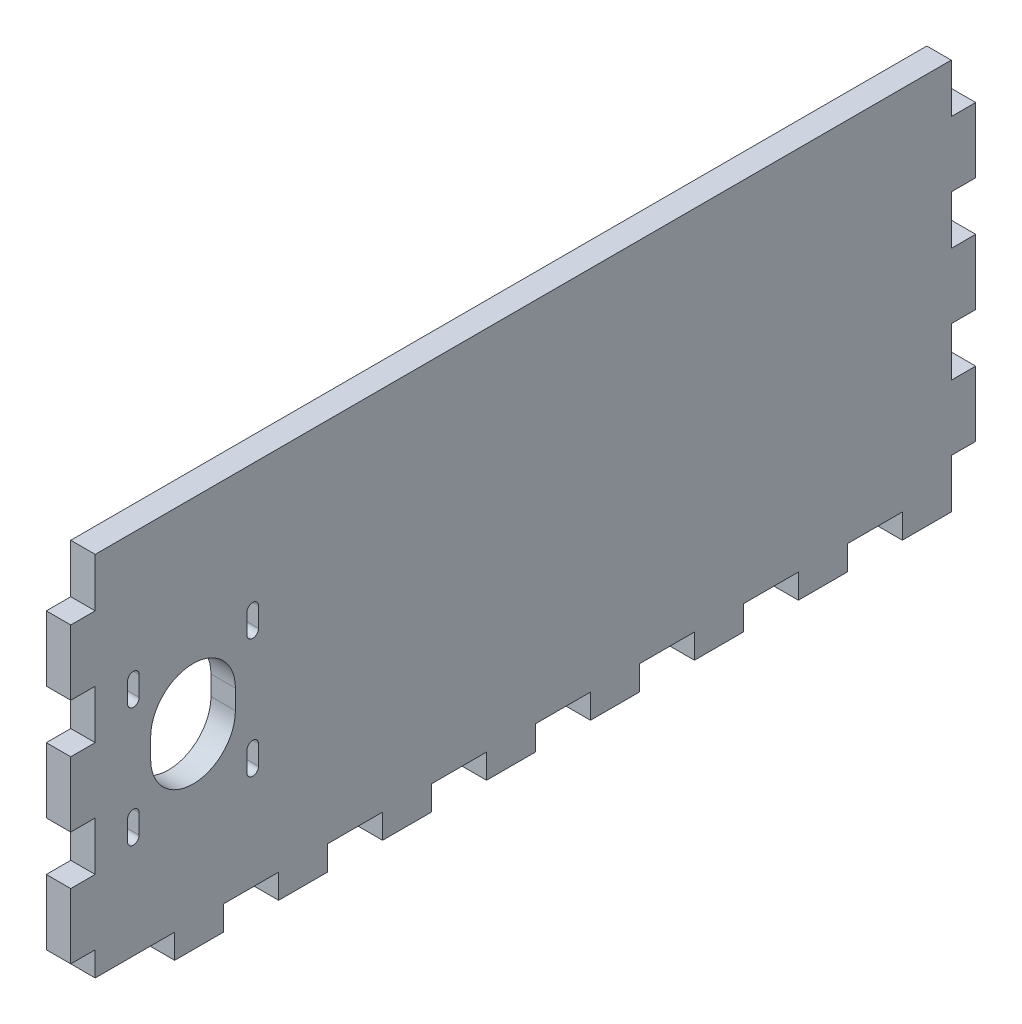
SolidWorks part; units mm, degrees
material "Acrylic (Medium-high impact)"
ref_plane "Front" through (0, 0, 0) normal (0, 0, 1) x (1, 0, 0)
ref_plane "Top" through (0, 0, 0) normal (0, 1, 0) x (1, 0, 0)
ref_plane "Right" through (0, 0, 0) normal (1, 0, 0) x (0, 0, -1)
sketch "Sketch1" plane through (0, 0, 0) normal (0, 0, 1) x (1, 0, 0)
  line L0 (0, 143.002) -> (0, -143.002) construction
  line L1 (-3.302, 133.858) -> (-3.302, -143.002)
  line L2 (-3.302, -143.002) -> (3.302, -143.002)
  line L3 (3.302, 143.002) -> (3.302, -143.002)
  line L4 (3.302, 143.002) -> (-16.256, 143.002)
  line L5 (-5.842, 136.398) -> (-16.256, 136.398)
  line L6 (-16.256, 143.002) -> (-16.256, 136.398)
  line L8 (-28.956, 155.448) -> (16.002, 155.448)
  line L9 (-28.956, 155.448) -> (-28.956, -149.352)
  line L10 (-28.956, -149.352) -> (16.002, -149.352)
  line L11 (16.002, 155.448) -> (16.002, -149.352)
  arc A0 (-3.302, 133.858) -> (-5.842, 136.398) centre (-5.842, 133.858) ccw
  point P2 (0, -143.002)
  point P11 (0, 0)
  dimension "D5" = 2.54
  dimension "D1" = 6.604
  dimension "D2" = 12.954
  dimension "D3" = 6.604
  dimension "D4" = 286.004
  dimension "D6" = 304.8
  dimension "D7" = 6.35
  dimension "D8" = 12.7
  dimension "D9" = 12.7
extrude "Boss-Extrude1" add sketch "Sketch1" along normal blind 6.35
sketch "Sketch2" plane through (16.002, 0, 0) normal (1, 0, 0) x (0, 0, -1)
  line L0 (-6.35, -149.352) -> (-6.35, 155.448) construction
  line L1 (-6.35, -47.752) -> (228.6, -47.752)
  line L2 (-6.35, -47.752) -> (-6.35, -149.352)
  line L3 (-6.35, -149.352) -> (228.6, -149.352)
  line L4 (228.6, -47.752) -> (228.6, -149.352)
  line L5 (14.4, -101.092) -> (14.4, -96.012)
  line L6 (36.4, -96.012) -> (36.4, -101.092)
  line L7 (8.4, -116.592) -> (8.4, -111.512)
  line L8 (11.4, -116.592) -> (11.4, -111.512)
  line L9 (8.4, -85.592) -> (8.4, -80.512)
  line L10 (11.4, -85.592) -> (11.4, -80.512)
  line L11 (25.4, -96.012) -> (25.4, -101.092) construction
  line L12 (42.4, -116.592) -> (42.4, -111.512)
  line L13 (39.4, -116.592) -> (39.4, -111.512)
  line L14 (39.4, -85.592) -> (39.4, -80.512)
  line L15 (42.4, -85.592) -> (42.4, -80.512)
  line L16 (0, -149.352) -> (0, 155.448) construction
  line L17 (225.425, -60.452) -> (225.425, -77.3853) construction
  line L18 (228.6, -47.752) -> (222.25, -47.752)
  line L19 (228.6, -47.752) -> (228.6, -60.452)
  line L20 (228.6, -60.452) -> (222.25, -60.452)
  line L21 (222.25, -47.752) -> (222.25, -60.452)
  line L22 (228.6, -107.0187) -> (222.25, -107.0187)
  line L23 (228.6, -107.0187) -> (228.6, -119.7187)
  line L24 (228.6, -119.7187) -> (222.25, -119.7187)
  line L25 (222.25, -107.0187) -> (222.25, -119.7187)
  line L26 (228.6, -136.652) -> (222.25, -136.652)
  line L27 (228.6, -136.652) -> (228.6, -149.352)
  line L28 (228.6, -149.352) -> (222.25, -149.352)
  line L29 (222.25, -136.652) -> (222.25, -149.352)
  line L30 (228.6, -77.3853) -> (222.25, -77.3853)
  line L31 (228.6, -77.3853) -> (228.6, -90.0853)
  line L32 (228.6, -90.0853) -> (222.25, -90.0853)
  line L33 (222.25, -77.3853) -> (222.25, -90.0853)
  line L34 (225.425, -90.0853) -> (225.425, -107.0187) construction
  line L35 (225.425, -119.7187) -> (225.425, -136.652) construction
  arc A0 (14.4, -101.092) -> (36.4, -101.092) centre (25.4, -101.092) ccw
  arc A1 (36.4, -96.012) -> (14.4, -96.012) centre (25.4, -96.012) ccw
  arc A2 (8.4, -116.592) -> (11.4, -116.592) centre (9.9, -116.592) ccw
  arc A3 (11.4, -111.512) -> (8.4, -111.512) centre (9.9, -111.512) ccw
  arc A4 (8.4, -85.592) -> (11.4, -85.592) centre (9.9, -85.592) ccw
  arc A5 (11.4, -80.512) -> (8.4, -80.512) centre (9.9, -80.512) ccw
  arc A6 (42.4, -116.592) -> (39.4, -116.592) centre (40.9, -116.592) cw
  arc A7 (39.4, -111.512) -> (42.4, -111.512) centre (40.9, -111.512) cw
  arc A8 (42.4, -85.592) -> (39.4, -85.592) centre (40.9, -85.592) cw
  arc A9 (39.4, -80.512) -> (42.4, -80.512) centre (40.9, -80.512) cw
  point P44 (25.4, -98.552)
  point P47 (-6.35, -98.552)
  line M17 (0, -149.352) -> (0, 155.448)
  line M19 (-6.35, 155.448) -> (-6.35, -149.352)
  line M20 (-6.35, -149.352) -> (0, -149.352)
  dimension "D1" = 22
  dimension "D6" = 1.5
  dimension "D10" = 1.5
  dimension "D2" = 5.08
  dimension "D3" = 5.08
  dimension "D4" = 15.5
  dimension "D5" = 15.5
  dimension "D7" = 15.5
  dimension "D8" = 15.5
  dimension "D9" = 5.08
  dimension "D11" = 25.4
  dimension "D12" = 50.8
  dimension "D13" = 203.2
  dimension "D14" = 12.7
  dimension "D15" = 6.35
extrude "Boss-Extrude2" add sketch "Sketch2" against normal blind 6.35 contours L33 L30 L4 L20 L21 L1 L3 L29 L26 L24 L25 L22 L32 A5 L10 A4 L9 A3 L8 A2 L7 A1 L6 A0 L5 L13 A7 L12 A6 L14 A9 L15 A8 M17 | L1 M19 M20 M17 region at (16.002, -98.552, -115.0085) region at (16.002, -98.552, 3.175)
sketch "Sketch3" plane through (9.652, 0, 0) normal (-1, 0, 0) x (0, 0, 1)
  line L0 (-222.25, -136.652) -> (-222.25, -149.352) construction
  line L1 (-222.25, -143.002) -> (0, -143.002)
  line L2 (-222.25, -143.002) -> (-222.25, -149.352)
  line L3 (-222.25, -149.352) -> (0, -149.352)
  line L4 (0, -143.002) -> (0, -149.352)
  dimension "D1" = 6.35
extrude "Boss-Extrude3" add sketch "Sketch3" along normal up to surface (38.608 mm away) up to face at (-28.956, 3.048, 3.175)
sketch "Sketch4" plane through (0, -149.352, 0) normal (0, -1, 0) x (1, 0, 0)
  line L0 (9.652, -20.6375) -> (9.652, -33.3375)
  line L1 (16.002, 6.35) -> (9.652, 6.35)
  line L2 (16.002, 6.35) -> (16.002, -6.35)
  line L3 (16.002, -6.35) -> (9.652, -6.35)
  line L4 (9.652, 6.35) -> (9.652, -6.35)
  line L5 (16.002, -20.6375) -> (9.652, -20.6375)
  line L6 (16.002, -20.6375) -> (16.002, -33.3375)
  line L7 (16.002, -33.3375) -> (9.652, -33.3375)
  line L8 (9.652, -47.625) -> (9.652, -60.325)
  line L9 (16.002, -47.625) -> (9.652, -47.625)
  line L10 (16.002, -47.625) -> (16.002, -60.325)
  line L11 (16.002, -60.325) -> (9.652, -60.325)
  line L12 (9.652, -74.6125) -> (9.652, -87.3125)
  line L13 (16.002, -74.6125) -> (9.652, -74.6125)
  line L14 (16.002, -74.6125) -> (16.002, -87.3125)
  line L15 (16.002, -87.3125) -> (9.652, -87.3125)
  line L16 (9.652, -101.6) -> (9.652, -114.3)
  line L17 (16.002, -101.6) -> (9.652, -101.6)
  line L18 (16.002, -101.6) -> (16.002, -114.3)
  line L19 (16.002, -114.3) -> (9.652, -114.3)
  line L20 (9.652, -128.5875) -> (9.652, -141.2875)
  line L21 (16.002, -128.5875) -> (9.652, -128.5875)
  line L22 (16.002, -128.5875) -> (16.002, -141.2875)
  line L23 (16.002, -141.2875) -> (9.652, -141.2875)
  line L24 (9.652, -155.575) -> (9.652, -168.275)
  line L25 (16.002, -155.575) -> (9.652, -155.575)
  line L26 (16.002, -155.575) -> (16.002, -168.275)
  line L27 (16.002, -168.275) -> (9.652, -168.275)
  line L28 (9.652, -182.5625) -> (9.652, -195.2625)
  line L29 (16.002, -182.5625) -> (9.652, -182.5625)
  line L30 (16.002, -182.5625) -> (16.002, -195.2625)
  line L31 (16.002, -195.2625) -> (9.652, -195.2625)
  line L32 (9.652, -209.55) -> (9.652, -222.25)
  line L33 (16.002, -209.55) -> (9.652, -209.55)
  line L34 (16.002, -209.55) -> (16.002, -222.25)
  line L35 (16.002, -222.25) -> (9.652, -222.25)
  line L36 (-6.477, 6.35) -> (-6.477, -222.25) construction
  line L37 (-28.956, 6.35) -> (16.002, 6.35) construction
  line L38 (-28.956, -222.25) -> (16.002, -222.25) construction
  line L39 (-22.606, 6.35) -> (-22.606, -222.25)
  line L40 (16.002, 6.35) -> (9.652, 6.35)
  line L41 (16.002, 6.35) -> (16.002, -222.25)
  line L42 (16.002, -222.25) -> (9.652, -222.25)
  line L43 (9.652, 6.35) -> (9.652, -222.25)
  line L44 (-28.956, -222.25) -> (-22.606, -222.25)
  line L45 (-28.956, 6.35) -> (-28.956, -222.25)
  line L46 (-28.956, 6.35) -> (-22.606, 6.35)
  line L47 (-28.956, -222.25) -> (-22.606, -222.25)
  line L48 (-28.956, -209.55) -> (-28.956, -222.25)
  line L49 (-28.956, -209.55) -> (-22.606, -209.55)
  line L50 (-22.606, -209.55) -> (-22.606, -222.25)
  line L51 (-28.956, -195.2625) -> (-22.606, -195.2625)
  line L52 (-28.956, -182.5625) -> (-28.956, -195.2625)
  line L53 (-28.956, -182.5625) -> (-22.606, -182.5625)
  line L54 (-22.606, -182.5625) -> (-22.606, -195.2625)
  line L55 (-28.956, -168.275) -> (-22.606, -168.275)
  line L56 (-28.956, -155.575) -> (-28.956, -168.275)
  line L57 (-28.956, -155.575) -> (-22.606, -155.575)
  line L58 (-22.606, -155.575) -> (-22.606, -168.275)
  line L59 (-28.956, -141.2875) -> (-22.606, -141.2875)
  line L60 (-28.956, -128.5875) -> (-28.956, -141.2875)
  line L61 (-28.956, -128.5875) -> (-22.606, -128.5875)
  line L62 (-22.606, -128.5875) -> (-22.606, -141.2875)
  line L63 (-28.956, -114.3) -> (-22.606, -114.3)
  line L64 (-28.956, -101.6) -> (-28.956, -114.3)
  line L65 (-28.956, -101.6) -> (-22.606, -101.6)
  line L66 (-22.606, -101.6) -> (-22.606, -114.3)
  line L67 (-28.956, -87.3125) -> (-22.606, -87.3125)
  line L68 (-28.956, -74.6125) -> (-28.956, -87.3125)
  line L69 (-28.956, -74.6125) -> (-22.606, -74.6125)
  line L70 (-22.606, -74.6125) -> (-22.606, -87.3125)
  line L71 (-28.956, -60.325) -> (-22.606, -60.325)
  line L72 (-28.956, -47.625) -> (-28.956, -60.325)
  line L73 (-28.956, -47.625) -> (-22.606, -47.625)
  line L74 (-22.606, -47.625) -> (-22.606, -60.325)
  line L75 (-28.956, -33.3375) -> (-22.606, -33.3375)
  line L76 (-28.956, -20.6375) -> (-28.956, -33.3375)
  line L77 (-28.956, -20.6375) -> (-22.606, -20.6375)
  line L78 (-22.606, 6.35) -> (-22.606, -6.35)
  line L79 (-28.956, -6.35) -> (-22.606, -6.35)
  line L80 (-28.956, 6.35) -> (-28.956, -6.35)
  line L81 (-28.956, 6.35) -> (-22.606, 6.35)
  line L82 (-22.606, -20.6375) -> (-22.606, -33.3375)
  line L83 (-16.129, 3.175) -> (-22.606, 3.175) construction
  line L85 (-28.956, 6.35) -> (-22.606, 6.35)
  line L86 (-28.956, 6.35) -> (-28.956, 0)
  line L87 (-28.956, 0) -> (-22.606, 0)
  line L88 (-22.606, 6.35) -> (-22.606, 0)
  line L92 (9.652, 6.35) -> (9.652, 0)
  line L93 (9.652, 6.35) -> (16.002, 6.35)
  line L94 (16.002, 6.35) -> (16.002, 0)
  line L95 (9.652, 0) -> (16.002, 0)
  line L96 (-28.956, 6.35) -> (16.002, 6.35)
  line L97 (-28.956, 6.35) -> (-28.956, 0)
  line L98 (-28.956, 0) -> (16.002, 0)
  line L99 (16.002, 6.35) -> (16.002, 0)
  line L100 (-9.652, 6.35) -> (-9.652, 0)
  line L101 (-9.652, 0) -> (-3.302, 0)
  line L102 (-3.302, 6.35) -> (-3.302, 0)
  line L103 (-9.652, 6.35) -> (-3.302, 6.35)
  line L104 (-9.779, 0) -> (-16.129, 0)
  line L105 (-9.779, 0) -> (-9.779, 6.35)
  line L106 (-9.779, 6.35) -> (-16.129, 6.35)
  line L107 (-16.129, 0) -> (-16.129, 6.35)
  line L108 (-9.779, 3.175) -> (-3.302, 3.175) construction
  line L109 (-3.302, 6.35) -> (-3.302, 0) construction
  line L111 (-28.956, 6.35) -> (16.002, 6.35)
  line L112 (-28.956, 6.35) -> (-28.956, 0)
  line L113 (-28.956, 0) -> (16.002, 0)
  line L114 (16.002, 6.35) -> (16.002, 0)
  line M38 (16.002, -222.25) -> (16.002, 6.35)
  line M39 (16.002, 6.35) -> (-28.956, 6.35)
  line M40 (-28.956, 6.35) -> (-28.956, -222.25)
  line M41 (-28.956, -222.25) -> (16.002, -222.25)
  dimension "D1" = 6.35
  dimension "D2" = 12.7
  dimension "D4" = 6.35
  dimension "D5" = 6.35
  dimension "D7" = 6.35
  dimension "D3" = 9
  dimension "D6" = 3
sketch "Sketch6" plane through (0, 0, 6.35) normal (0, 0, 1) x (1, 0, 0)
  line L1 (16.002, -60.452) -> (9.652, -60.452)
  line L2 (16.002, -60.452) -> (16.002, -77.3853)
  line L3 (16.002, -77.3853) -> (9.652, -77.3853)
  line L4 (9.652, -60.452) -> (9.652, -77.3853)
  line L5 (16.002, -90.0853) -> (9.652, -90.0853)
  line L6 (16.002, -90.0853) -> (16.002, -107.0187)
  line L7 (16.002, -107.0187) -> (9.652, -107.0187)
  line L8 (9.652, -90.0853) -> (9.652, -107.0187)
  line L9 (16.002, -119.7187) -> (9.652, -119.7187)
  line L10 (16.002, -119.7187) -> (16.002, -136.652)
  line L11 (16.002, -136.652) -> (9.652, -136.652)
  line L12 (9.652, -119.7187) -> (9.652, -136.652)
  line L13 (-28.956, -149.352) -> (16.002, -149.352) construction
  line L14 (16.002, -47.752) -> (9.652, -47.752)
  line L15 (16.002, -47.752) -> (16.002, -149.352)
  line L16 (16.002, -149.352) -> (9.652, -149.352)
  line L17 (9.652, -47.752) -> (9.652, -149.352)
  line M1 (16.002, -149.352) -> (16.002, 155.448)
  line M4 (-28.956, -149.352) -> (16.002, -149.352)
sketch "Sketch7" plane through (16.002, 0, 0) normal (1, 0, 0) x (0, 0, -1)
  line L1 (-6.35, 180.723) -> (327.0227, 180.723)
  line L2 (-6.35, 180.723) -> (-6.35, -143.002)
  line L3 (-6.35, -143.002) -> (327.0227, -143.002)
  line L4 (327.0227, 180.723) -> (327.0227, -143.002)
  line L5 (-6.35, -149.352) -> (-6.35, 155.448) construction
  line L6 (222.25, -143.002) -> (0, -143.002) construction
  point P10 (160.3364, -143.002)
extrude "Cut-Extrude1" [suppressed] cut sketch "Sketch7" against normal through all
extrude "Cut-Extrude2" [suppressed] cut sketch "Sketch4" against normal blind 6.35 contours L87 L80 L79 L78 | L87 L39 M40 M39 | L107 L98 L105 L96 | L4 L95 L41 M39 | L95 L43 L3 M38 | L7 L5 L0 M38 | L77 L45 L75 L39 | L73 L45 L71 L39 | L69 L45 L67 L39 | L65 L45 L63 L39 | L61 L45 L59 L39 | L57 L45 L55 L39 | L53 L45 L51 L39 | L49 L45 L39 M41 | L33 L32 M38 M41 | L27 L25 L24 M38 | L23 L21 L20 M38 | L19 L17 L16 M38 | L15 L13 L12 M38 | L11 L9 L8 M38 | L31 L29 L28 M38
sketch "Sketch8" plane through (0, 0, 6.35) normal (0, 0, 1) x (1, 0, 0)
  line L0 (-28.956, -149.352) -> (16.002, -149.352) construction
  line L1 (9.652, -149.352) -> (-54.2235, -149.352)
  line L2 (9.652, -149.352) -> (9.652, 165.6994)
  line L3 (9.652, 165.6994) -> (-54.2235, 165.6994)
  line L4 (-54.2235, -149.352) -> (-54.2235, 165.6994)
  line L5 (9.652, -60.452) -> (9.652, -77.3853) construction
  line L7 (16.002, -47.752) -> (9.652, -47.752)
  line L8 (16.002, -47.752) -> (16.002, 165.6994)
  line L9 (16.002, 165.6994) -> (9.652, 165.6994)
  line L10 (9.652, -47.752) -> (9.652, 165.6994)
  line M6 (16.002, 155.448) -> (-28.956, 155.448)
  line M7 (-28.956, 155.448) -> (-28.956, -149.352)
  line M8 (-28.956, -149.352) -> (16.002, -149.352)
  line M9 (-16.256, 143.002) -> (3.302, 143.002)
  line M10 (3.302, 143.002) -> (3.302, -143.002)
  line M11 (3.302, -143.002) -> (-3.302, -143.002)
  line M12 (-3.302, -143.002) -> (-3.302, 133.858)
  arc M13 (-3.302, 133.858) -> (-5.842, 136.398) centre (-5.842, 133.858) ccw
  line M14 (-5.842, 136.398) -> (-16.256, 136.398)
  line M15 (-16.256, 136.398) -> (-16.256, 143.002)
extrude "Cut-Extrude4" cut sketch "Sketch8" against normal through all and the other way through all contours L2 M8 M6 M7 M15 M9 M10 M11 M12 M13 M14 | L4 L1 L2 L3 M7 M6 | L10 L7 L8 L9 region at (-11.5135, 2.4233, 6.35) region at (-40.0771, 15.3918, 6.35)
extrude "Cut-Extrude5" cut sketch "Sketch6" against normal blind 6.35 contours L14 L17 L1 M1 | L3 L17 L5 M1 | L7 L17 L9 M1 | L11 L17 M4 M1 region at (12.827, -54.102, 6.35) region at (12.827, -83.7353, 6.35) region at (12.827, -113.3687, 6.35) region at (12.827, -143.002, 6.35)
extrude "Cut-Extrude6" cut sketch "Sketch4<3>" against normal blind 6.35 contours L3 L43 L5 M38 | L7 L43 L9 M38 | L11 L43 L13 M38 | L15 L43 L17 M38 | L19 L43 L21 M38 | L23 L43 L25 M38 | L27 L43 L29 M38 | L31 L43 L33 M38 | L95 L43 L3 M38 | L4 L95 L41 M39 region at (12.827, -149.352, -13.4938) region at (12.827, -149.352, -40.4813) region at (12.827, -149.352, -3.175) region at (12.827, -149.352, 3.175) region at (12.827, -149.352, -67.4688) region at (12.827, -149.352, -94.4563) region at (12.827, -149.352, -121.4438) region at (12.827, -149.352, -148.4313) region at (12.827, -149.352, -175.4188) region at (12.827, -149.352, -202.4063)
sketch "Sketch4<3>" plane through (0, -149.352, 0) normal (0, -1, 0) x (1, 0, 0) same geometry as "Sketch4"
